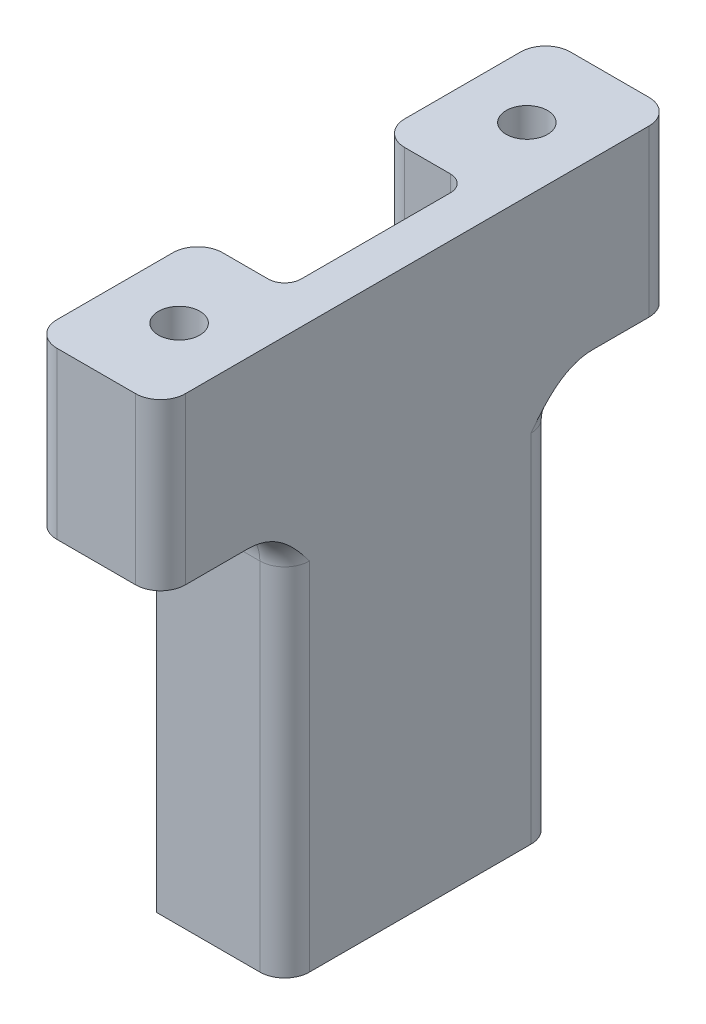
SolidWorks part; units mm, degrees
material "K110"
ref_plane "Front Plane" through (0, 0, 0) normal (0, 0, 1) x (1, 0, 0)
ref_plane "Top Plane" through (0, 0, 0) normal (0, 1, 0) x (1, 0, 0)
ref_plane "Right Plane" through (0, 0, 0) normal (1, 0, 0) x (0, 0, -1)
sketch "Sketch1" plane through (0, 0, 0) normal (0, 1, 0) x (1, 0, 0)
  line L0 (4.37, 30.63) -> (-5.13, 30.63) construction
  line L1 (-8.13, -31.37) -> (7.37, -31.37)
  line L2 (-8.13, -31.37) -> (-8.13, 30.63)
  line L3 (-8.13, 30.63) -> (7.37, 30.63)
  line L4 (7.37, -31.37) -> (7.37, 30.63)
  line L5 (-8.13, 27.63) -> (-8.13, 13.63) construction
  line L6 (7.37, -28.37) -> (7.37, 27.63) construction
  line L7 (-5.13, -31.37) -> (4.37, -31.37) construction
  point P0 (0, 0)
extrude "Boss-Extrude1" add sketch "Sketch1" against normal blind 68
fillet "Fillet1" radius 3 4 edges at (-8.13, -34, -30.63) (7.37, -34, -30.63) (-8.13, -34, 31.37) (7.37, -34, 31.37)
sketch "Sketch2" plane through (0, 0, 0) normal (0, 1, 0) x (1, 0, 0)
  line L0 (-5.13, 10.63) -> (0.37, 10.63) construction
  line L1 (2.37, 8.63) -> (2.37, -9.37) construction
  line L2 (0.37, -11.37) -> (-5.13, -11.37) construction
  line L3 (-5.13, 10.63) -> (0.37, 10.63)
  line L4 (2.37, 8.63) -> (2.37, -9.37)
  line L5 (0.37, -11.37) -> (-5.13, -11.37)
  line L6 (-8.13, 13.63) -> (-8.13, -14.37)
  arc A0 (-8.13, 13.63) -> (-5.13, 10.63) centre (-5.13, 13.63) ccw construction
  arc A1 (2.37, 8.63) -> (0.37, 10.63) centre (0.37, 8.63) ccw construction
  arc A2 (0.37, -11.37) -> (2.37, -9.37) centre (0.37, -9.37) ccw construction
  arc A3 (-5.13, -11.37) -> (-8.13, -14.37) centre (-5.13, -14.37) ccw construction
  arc A4 (-8.13, 13.63) -> (-5.13, 10.63) centre (-5.13, 13.63) ccw
  arc A5 (2.37, 8.63) -> (0.37, 10.63) centre (0.37, 8.63) ccw
  arc A6 (0.37, -11.37) -> (2.37, -9.37) centre (0.37, -9.37) ccw
  arc A7 (-5.13, -11.37) -> (-8.13, -14.37) centre (-5.13, -14.37) ccw
extrude "Cut-Extrude1" cut sketch "Sketch2" against normal up to next
sketch "Sketch3" plane through (0, -68, 0) normal (0, 1, 0) x (1, 0, 0)
  line L1 (-5.13, -31.37) -> (4.37, -31.37) construction
  line L2 (7.37, -28.37) -> (7.37, 27.63) construction
  line L3 (-8.13, -14.37) -> (-8.13, -28.37) construction
  line L4 (4.37, -16.37) -> (-8.13, -16.37) construction
  line L5 (4.37, -16.37) -> (-8.13, -16.37)
  line L6 (-8.13, -16.37) -> (-8.13, -28.37)
  line L7 (7.37, -28.37) -> (7.37, -13.37)
  line L8 (-5.13, -31.37) -> (4.37, -31.37)
  arc A0 (-8.13, -28.37) -> (-5.13, -31.37) centre (-5.13, -28.37) ccw construction
  arc A1 (4.37, -31.37) -> (7.37, -28.37) centre (4.37, -28.37) ccw construction
  arc A2 (4.37, -16.37) -> (7.37, -13.37) centre (4.37, -13.37) ccw construction
  arc A3 (4.37, -16.37) -> (7.37, -13.37) centre (4.37, -13.37) ccw
  arc A4 (4.37, -31.37) -> (7.37, -28.37) centre (4.37, -28.37) ccw
  arc A5 (-8.13, -28.37) -> (-5.13, -31.37) centre (-5.13, -28.37) ccw
extrude "Cut-Extrude2" cut sketch "Sketch3" along normal up to surface (48 mm away)
mirror "Mirror1" about plane through (0, 0, 0) normal (0, 0, 1) of "Cut-Extrude2"
fillet "Fillet2" radius 5 4 edges at (6.4913, -20, -15.4913) (6.4913, -20, 15.4913) (-1.88, -20, -16.37) (-1.88, -20, 16.37)
hole_wizard "M6 Tapped Hole1" positions "Sketch6" profile "Sketch5" tap size "M6" standard "ISO"
sketch "Sketch6" plane through (0, 0, 0) normal (0, 1, 0) x (1, 0, 0)
  line L0 (-0.38, 30.63) -> (-0.38, 10.63) construction
  line L1 (4.37, 30.63) -> (-5.13, 30.63) construction
  line L2 (0.37, 10.63) -> (-5.13, 10.63) construction
  line L4 (-0.38, -31.37) -> (-0.38, -11.37) construction
  line L5 (-5.13, -31.37) -> (4.37, -31.37) construction
  line L6 (-5.13, -11.37) -> (0.37, -11.37) construction
  point P0 (-0.38, 20.63)
  point P2 (-0.38, -21.37)
sketch "Sketch5" plane through (-0.38, 0, -20.63) normal (1, 0, 0) x (0, 0, 1)
  line L0 (0, 0) -> (0, 16.5022)
  line L1 (0, 16.5022) -> (2.5, 15)
  line L2 (2.5, 15) -> (2.5, 0)
  line L5 (2.5, 0) -> (0, 0)
  line L10 (0, 16.5022) -> (-2.5, 15) construction
  line L11 (0, -6.35) -> (0, 107.95) construction
  dimension "Tap Drill Dia." = 5
  dimension "Tap Drill Depth" = 15
  dimension "Drill Angle" = 118
cosmetic thread "Hole Thread1"
cosmetic thread "Hole Thread2"
